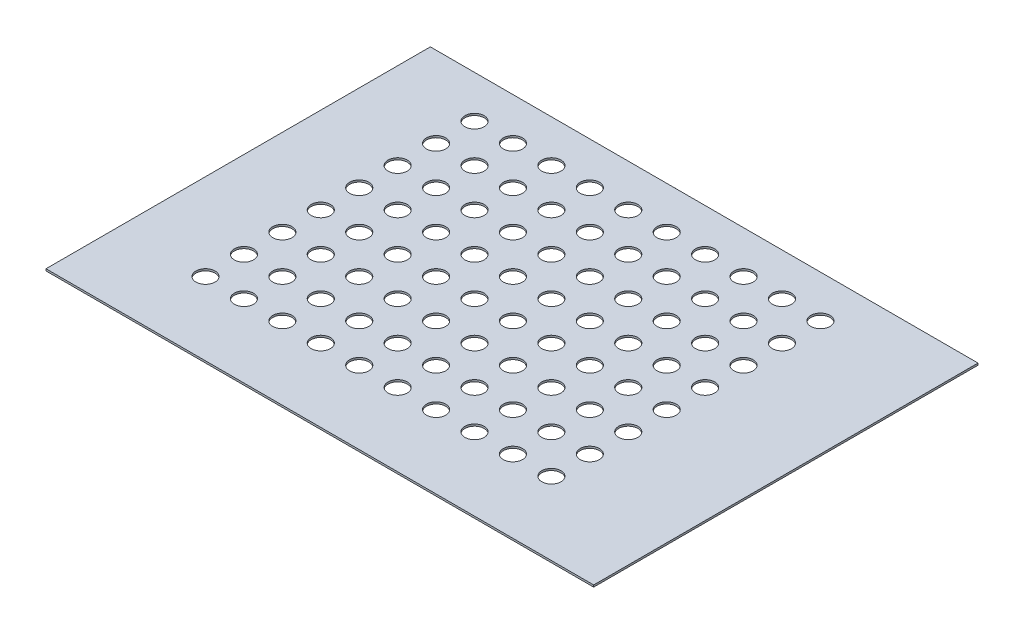
SolidWorks part; units mm, degrees
ref_plane "Front Plane" through (0, 0, 0) normal (0, 0, 1) x (1, 0, 0)
ref_plane "Top Plane" through (0, 0, 0) normal (0, 1, 0) x (1, 0, 0)
ref_plane "Right Plane" through (0, 0, 0) normal (1, 0, 0) x (0, 0, -1)
sketch "Sketch1" plane through (0, 0, 0) normal (0, 1, 0) x (1, 0, 0)
  line L1 (-108.5034, 75.9524) -> (176.4966, 75.9524)
  line L2 (-108.5034, 75.9524) -> (-108.5034, -124.0476)
  line L3 (-108.5034, -124.0476) -> (176.4966, -124.0476)
  line L4 (176.4966, 75.9524) -> (176.4966, -124.0476)
  dimension "D1" = 285
  dimension "D2" = 200
base flange "Base-Flange1" sketch "Sketch1" thickness 1 reverse thickness direction no parameters "D1"=0.7366
sketch "Sketch2" plane through (0, 0, 0) normal (0, 1, 0) x (1, 0, 0)
  line L0 (-108.5034, 75.9524) -> (-108.5034, -124.0476) construction
  circle A0 centre (-63.5034, 53.9521) radius 5
  circle A1 centre (-63.5034, 33.9521) radius 5
  circle A2 centre (-63.5034, 13.9521) radius 5
  circle A3 centre (-63.5034, -6.0479) radius 5
  circle A4 centre (-63.5034, -26.0479) radius 5
  circle A5 centre (-63.5034, -46.0479) radius 5
  circle A48 centre (-63.5034, -66.0479) radius 5
  circle A49 centre (-63.5034, -86.0479) radius 5
  circle A64 centre (-43.5034, 53.9521) radius 5
  circle A65 centre (-43.5034, 33.9521) radius 5
  circle A66 centre (-43.5034, 13.9521) radius 5
  circle A67 centre (-43.5034, -6.0479) radius 5
  circle A68 centre (-43.5034, -26.0479) radius 5
  circle A69 centre (-43.5034, -46.0479) radius 5
  circle A70 centre (-43.5034, -66.0479) radius 5
  circle A71 centre (-43.5034, -86.0479) radius 5
  circle A72 centre (-23.5034, 53.9521) radius 5
  circle A73 centre (-23.5034, 33.9521) radius 5
  circle A74 centre (-23.5034, 13.9521) radius 5
  circle A75 centre (-23.5034, -6.0479) radius 5
  circle A76 centre (-23.5034, -26.0479) radius 5
  circle A77 centre (-23.5034, -46.0479) radius 5
  circle A78 centre (-23.5034, -66.0479) radius 5
  circle A79 centre (-23.5034, -86.0479) radius 5
  circle A80 centre (-3.5034, 53.9521) radius 5
  circle A81 centre (-3.5034, 33.9521) radius 5
  circle A82 centre (-3.5034, 13.9521) radius 5
  circle A83 centre (-3.5034, -6.0479) radius 5
  circle A84 centre (-3.5034, -26.0479) radius 5
  circle A85 centre (-3.5034, -46.0479) radius 5
  circle A86 centre (-3.5034, -66.0479) radius 5
  circle A87 centre (-3.5034, -86.0479) radius 5
  circle A88 centre (16.4966, 53.9521) radius 5
  circle A89 centre (16.4966, 33.9521) radius 5
  circle A90 centre (16.4966, 13.9521) radius 5
  circle A91 centre (16.4966, -6.0479) radius 5
  circle A92 centre (16.4966, -26.0479) radius 5
  circle A93 centre (16.4966, -46.0479) radius 5
  circle A94 centre (16.4966, -66.0479) radius 5
  circle A95 centre (16.4966, -86.0479) radius 5
  circle A96 centre (36.4966, 53.9521) radius 5
  circle A97 centre (36.4966, 33.9521) radius 5
  circle A98 centre (36.4966, 13.9521) radius 5
  circle A99 centre (36.4966, -6.0479) radius 5
  circle A100 centre (36.4966, -26.0479) radius 5
  circle A101 centre (36.4966, -46.0479) radius 5
  circle A102 centre (36.4966, -66.0479) radius 5
  circle A103 centre (36.4966, -86.0479) radius 5
  circle A104 centre (56.4966, 53.9521) radius 5
  circle A105 centre (56.4966, 33.9521) radius 5
  circle A106 centre (56.4966, 13.9521) radius 5
  circle A107 centre (56.4966, -6.0479) radius 5
  circle A108 centre (56.4966, -26.0479) radius 5
  circle A109 centre (56.4966, -46.0479) radius 5
  circle A110 centre (56.4966, -66.0479) radius 5
  circle A111 centre (56.4966, -86.0479) radius 5
  circle A112 centre (76.4966, 53.9521) radius 5
  circle A113 centre (76.4966, 33.9521) radius 5
  circle A114 centre (76.4966, 13.9521) radius 5
  circle A115 centre (76.4966, -6.0479) radius 5
  circle A116 centre (76.4966, -26.0479) radius 5
  circle A117 centre (76.4966, -46.0479) radius 5
  circle A118 centre (76.4966, -66.0479) radius 5
  circle A119 centre (76.4966, -86.0479) radius 5
  circle A120 centre (96.4966, 53.9521) radius 5
  circle A121 centre (96.4966, 33.9521) radius 5
  circle A122 centre (96.4966, 13.9521) radius 5
  circle A123 centre (96.4966, -6.0479) radius 5
  circle A124 centre (96.4966, -26.0479) radius 5
  circle A125 centre (96.4966, -46.0479) radius 5
  circle A126 centre (96.4966, -66.0479) radius 5
  circle A127 centre (96.4966, -86.0479) radius 5
  circle A128 centre (116.4966, 53.9521) radius 5
  circle A129 centre (116.4966, 33.9521) radius 5
  circle A130 centre (116.4966, 13.9521) radius 5
  circle A131 centre (116.4966, -6.0479) radius 5
  circle A132 centre (116.4966, -26.0479) radius 5
  circle A133 centre (116.4966, -46.0479) radius 5
  circle A134 centre (116.4966, -66.0479) radius 5
  circle A135 centre (116.4966, -86.0479) radius 5
  dimension "D1" = 10
  dimension "D5" = 20
  dimension "D6" = 45
  dimension "D2" = 8
extrude "Cut-Extrude1" cut sketch "Sketch2" against normal through all normal cut yes
sketch "Bend-Lines1" [suppressed] plane through (0, 0, 0) normal (0, 1, 0) x (1, 0, 0)
sketch "Bounding-Box1" [suppressed] plane through (0, 0, 0) normal (0, 1, 0) x (1, 0, 0)
sheet metal parameters "Sheet-Metal1" thickness 1 parameters "D1"=0.7366
flat pattern "Flat-Pattern1" [suppressed]
sketch "Bend-Lines2" plane through (0, 0, 0) normal (0, 1, 0) x (1, 0, 0)
sketch3d "Bounding-Box2" [suppressed]
  line L0 (176.4966, -124.0476, 0) -> (-108.5034, -124.0476, 0) construction
  line L1 (176.4966, 75.9524, 0) -> (-108.5034, 75.9524, 0) construction
  line L2 (176.4966, -124.0476, 0) -> (176.4966, 75.9524, 0) construction
  line L3 (-108.5034, -124.0476, 0) -> (-108.5034, 75.9524, 0) construction
sheet metal parameters "Sheet-Metal2" thickness 1 parameters "D1"=0.7366
flat pattern "Flat-Pattern1"
sketch "Bend-Lines2" plane through (0, 0, 0) normal (0, 1, 0) x (1, 0, 0)
sketch3d "Bounding-Box2" [suppressed]
  line L0 (176.4966, -124.0476, 0) -> (-108.5034, -124.0476, 0) construction
  line L1 (176.4966, 75.9524, 0) -> (-108.5034, 75.9524, 0) construction
  line L2 (176.4966, -124.0476, 0) -> (176.4966, 75.9524, 0) construction
  line L3 (-108.5034, -124.0476, 0) -> (-108.5034, 75.9524, 0) construction
